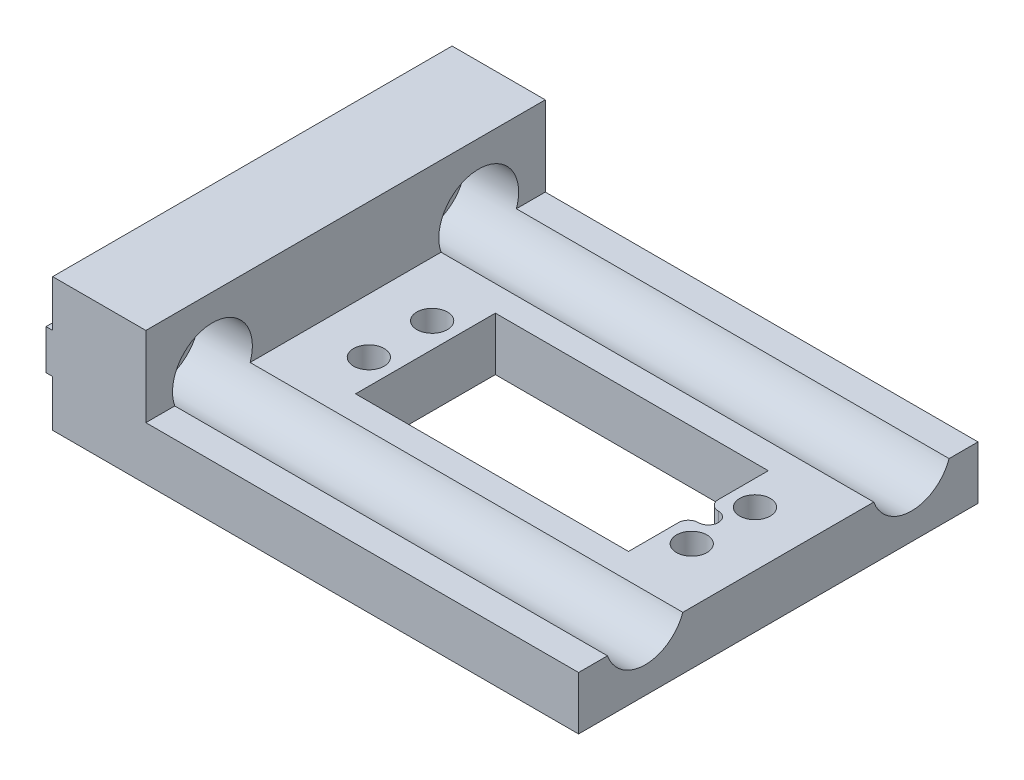
SolidWorks part; units mm, degrees
ref_plane "Alzado" through (0, 0, 0) normal (0, 0, 1) x (1, 0, 0)
ref_plane "Planta" through (0, 0, 0) normal (0, 1, 0) x (1, 0, 0)
ref_plane "Vista lateral" through (0, 0, 0) normal (1, 0, 0) x (0, 0, -1)
sketch "Croquis1" plane through (0, 0, 0) normal (0, 0, 1) x (1, 0, 0)
  line L0 (0, 0) -> (0, -7)
  line L1 (0, -7) -> (-1, -7)
  line L2 (-1, -7) -> (-1, -13)
  line L3 (-1, -13) -> (0, -13)
  line L4 (0, -13) -> (0, -20)
  line L5 (0, -20) -> (79, -20)
  line L6 (79, -20) -> (79, -12)
  line L7 (79, -12) -> (14, -12)
  line L8 (14, -12) -> (14, 0)
  line L9 (14, 0) -> (0, 0)
  point P3 (0, 0)
  point P12 (-1, -10)
  point P13 (-0.1137, 0)
  dimension "D1" = 20
  dimension "D2" = 6
  dimension "D3" = 10
  dimension "D4" = 1
  dimension "D5" = 14
  dimension "D6" = 65
  dimension "D7" = 12
extrude "Saliente-Extruir1" add sketch "Croquis1" along normal blind 60
sketch "Croquis2" plane through (14, 0, 0) normal (1, 0, 0) x (0, 0, -1)
  line L0 (-60, 0) -> (0, 0) construction
  line L1 (0, -12) -> (0, 0) construction
  line L2 (-60, -12) -> (-60, 0) construction
  circle A0 centre (-50, -10) radius 2.75
  circle A1 centre (-10, -10) radius 2.75
  dimension "D1" = 5.5
  dimension "D2" = 5.5
  dimension "D3" = 10
  dimension "D4" = 10
  dimension "D5" = 10
  dimension "D6" = 10
extrude "Cortar-Extruir1" cut sketch "Croquis2" against normal through all
sketch "Croquis4" plane through (79, 0, 0) normal (1, 0, 0) x (0, 0, -1)
  circle A0 centre (-50, -10) radius 6
  circle A1 centre (-10, -10) radius 6
  dimension "D1" = 12
  dimension "D2" = 12
extrude "Cortar-Extruir2" cut sketch "Croquis4" against normal blind 73
sketch "Croquis5" plane through (0, -12, 0) normal (0, 1, 0) x (1, 0, 0)
  line L0 (79, -55.6569) -> (14, -55.6569) construction
  line L1 (26, -19.5) -> (67, -19.5)
  line L2 (26, -19.5) -> (26, -40.5)
  line L3 (26, -40.5) -> (67, -40.5)
  line L4 (67, -19.5) -> (67, -40.5)
  line L5 (26, -19.5) -> (67, -40.5) construction
  line L6 (26, -40.5) -> (67, -19.5) construction
  line L7 (79, -44.3431) -> (79, -15.6569) construction
  point P0 (46.5, -30)
  point P7 (46.5, -55.6569)
  point P10 (79, -30)
  dimension "D1" = 21
  dimension "D2" = 41
  dimension "D3" = 0
  dimension "D4" = 0
extrude "Cortar-Extruir3" cut sketch "Croquis5" against normal through all
sketch "Croquis6" plane through (0, -12, 0) normal (0, 1, 0) x (1, 0, 0)
  line L1 (22.25, -25.25) -> (70.75, -25.25) construction
  line L2 (22.25, -25.25) -> (22.25, -34.75) construction
  line L3 (22.25, -34.75) -> (70.75, -34.75) construction
  line L4 (70.75, -25.25) -> (70.75, -34.75) construction
  line L5 (22.25, -25.25) -> (70.75, -34.75) construction
  line L6 (22.25, -34.75) -> (70.75, -25.25) construction
  circle A0 centre (22.25, -25.25) radius 2.3
  circle A1 centre (22.25, -34.75) radius 2.3
  circle A2 centre (70.75, -25.25) radius 2.3
  circle A3 centre (70.75, -34.75) radius 2.3
  point P0 (46.5, -30)
  dimension "D3" = 4.6
  dimension "D4" = 4.6
  dimension "D5" = 4.6
  dimension "D6" = 4.6
  dimension "D1" = 48.5
  dimension "D2" = 9.5
extrude "Cortar-Extruir4" cut sketch "Croquis6" against normal through all
sketch "Croquis7" plane through (14, -12, 60) normal (0, 1, 0) x (1, 0, 0)
  line L0 (53, 19.5) -> (53, 40.5) construction
  line L1 (53, 28.5) -> (56, 28.5)
  line L2 (53, 28.5) -> (53, 31.5)
  line L3 (53, 31.5) -> (56, 31.5)
  line L4 (56, 28.5) -> (56, 31.5)
  point P6 (53, 30)
  point P7 (53, 30)
  dimension "D1" = 0
  dimension "D2" = 3
  dimension "D3" = 3
extrude "Cortar-Extruir5" cut sketch "Croquis7" against normal through all
fillet "Redondeo3" radius 1.5 4 edges at (67, -16, 28.5) (67, -16, 31.5) (70, -16, 31.5) (70, -16, 28.5)
